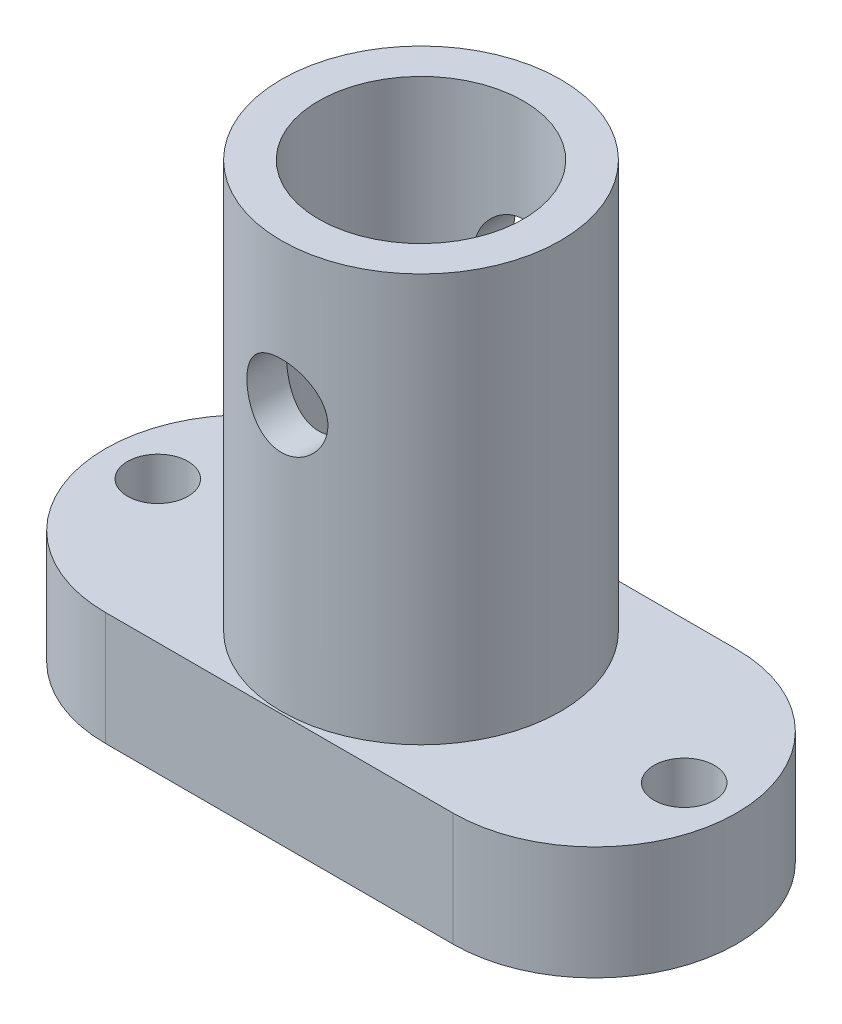
SolidWorks part; units mm, degrees
ref_plane "Front Plane" through (0, 0, 0) normal (0, 0, 1) x (1, 0, 0)
ref_plane "Top Plane" through (0, 0, 0) normal (0, 1, 0) x (1, 0, 0)
ref_plane "Right Plane" through (0, 0, 0) normal (1, 0, 0) x (0, 0, -1)
sketch "Sketch1" plane through (0, 0, 0) normal (0, 1, 0) x (1, 0, 0)
  line L0 (3.6045, 0) -> (17.6045, 0) construction
  line L1 (3.6045, 5.715) -> (17.6045, 5.715)
  line L2 (3.6045, -5.715) -> (17.6045, -5.715)
  arc A0 (3.6045, 5.715) -> (3.6045, -5.715) centre (3.6045, 0) ccw
  arc A1 (17.6045, -5.715) -> (17.6045, 5.715) centre (17.6045, 0) ccw
  circle A4 centre (10.6045, 0) radius 5.625
  circle A5 centre (10.6045, 0) radius 4.125
  circle A6 centre (0, 0) radius 1.2192
  circle A7 centre (21.209, 0) radius 1.2192
  point P2 (0, 0)
  point P3 (10.6045, 0)
  point P15 (47.7112, 5.715)
  point P16 (34.0907, 0)
  point P17 (27.5676, 0)
  point P18 (0, 0)
  point P19 (0, 0)
  point P20 (0, 0)
  point P21 (31.1457, 0.273)
  point P22 (39.7337, 0.3581)
  point P23 (0, 0)
  dimension "D1" = 5.715
  dimension "D4" = 2.4384
  dimension "D2" = 8.25
  dimension "D3" = 1.5
  dimension "D5" = 21.209
  dimension "D6" = 10.6045
  dimension "D7" = 14
extrude "Boss-Extrude1" add sketch "Sketch1" along normal blind 4.572 contours L2 A1 L1 A0 A6 A4 A7 | A5 L0 | A4 L0 A5 | L0 A4 A5 | L0 A5 region at (10.6045, 0, -4.2508) region at (10.6045, 0, 1.7507) region at (10.6045, 0, -1.7507) region at (15.4795, 0, 0.1258) region at (10.6045, 0, -5.6871)
extrude "Boss-Extrude2" add sketch "Sketch1<3>" along normal blind 21 contours A4 L0 A5 | L0 A4 A5 region at (10.6045, 0, -4.2508) region at (15.4795, 0, 0.1258)
sketch "Sketch1<3>" plane through (0, 0, 0) normal (0, 1, 0) x (1, 0, 0) same geometry as "Sketch1"
sketch "Sketch2" plane through (0, 0, 0) normal (0, 0, 1) x (1, 0, 0)
  line L0 (3.6045, 0) -> (17.6045, 0) construction
  circle A0 centre (10.6045, 15.24) radius 1.632
  point P4 (10.6045, 0)
  point P5 (10.6045, 14.7614)
  dimension "D1" = 3.2639
  dimension "D2" = 15.24
extrude "Cut-Extrude1" cut sketch "Sketch2" along normal blind 18.923 and the other way blind 18.923
equation "\"D6@Sketch1\"=\"D5@Sketch1\"/2"
